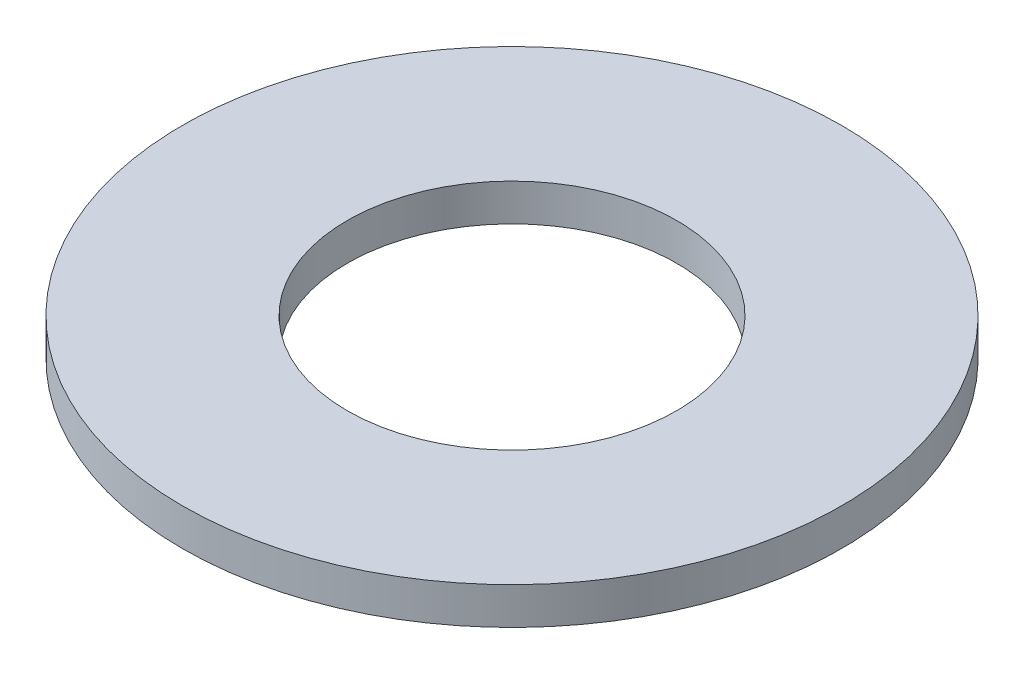
SolidWorks part; units mm, degrees
ref_plane "Front Plane" through (0, 0, 0) normal (0, 0, 1) x (1, 0, 0)
ref_plane "Top Plane" through (0, 0, 0) normal (0, 1, 0) x (1, 0, 0)
ref_plane "Right Plane" through (0, 0, 0) normal (1, 0, 0) x (0, 0, -1)
sketch "Sketch1" plane through (0, 0, 0) normal (0, 1, 0) x (1, 0, 0)
  circle A0 centre (0, 0) radius 80
  dimension "FLANGE_OD" = 160
extrude "Boss-Extrude1" add sketch "Sketch1" along normal blind 9
sketch "Sketch2" plane through (0, 0, 0) normal (0, 1, 0) x (1, 0, 0)
  circle A0 centre (0, 0) radius 40
  dimension "BORE_D" = 80
extrude "Cut-Extrude1" cut sketch "Sketch2" along normal through all
sketch "Sketch3" plane through (0, 9, 0) normal (0, 1, 0) x (1, 0, 0)
  circle A0 centre (0, 0) radius 32.0415 construction
  circle A1 centre (-32.0415, 0) radius 6.3334
  dimension "BOLT_D" = 12.6669
  dimension "BOLT_PCD" = 64.083
extrude "Cut-Extrude2" cut sketch "Sketch3" against normal blind 7.6576 rebuild error yes
pattern_circular "CirPattern1" count 5 over 360 rebuild error yes
